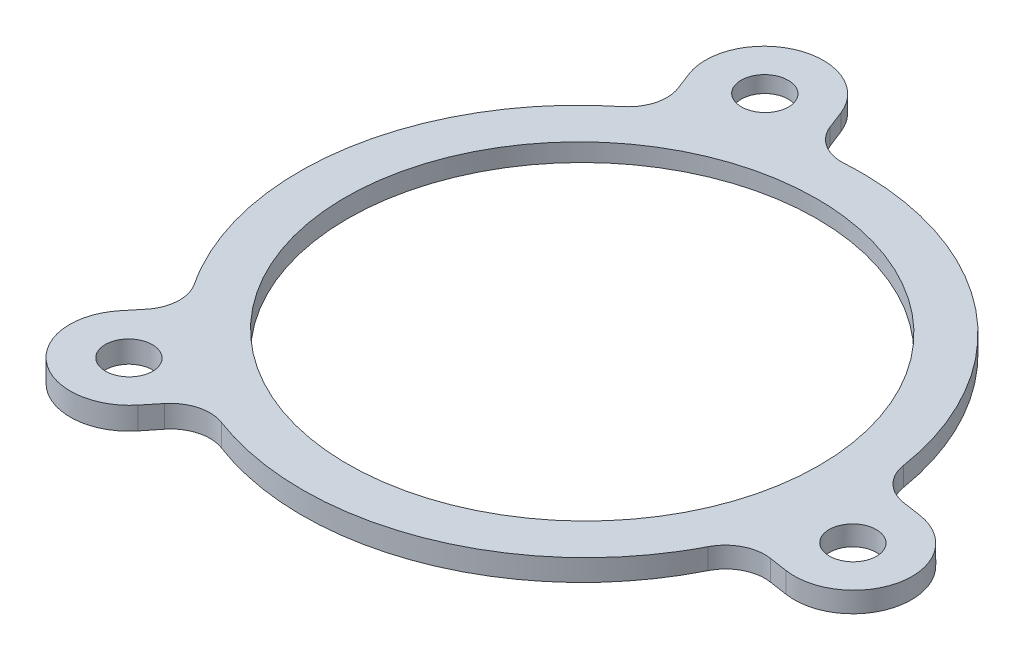
SolidWorks part; units mm, degrees
material "5454-O"
ref_plane "Front Plane" through (0, 0, 0) normal (0, 0, 1) x (1, 0, 0)
ref_plane "Top Plane" through (0, 0, 0) normal (0, 1, 0) x (1, 0, 0)
ref_plane "Right Plane" through (0, 0, 0) normal (1, 0, 0) x (0, 0, -1)
sketch "Sketch1" plane through (0, 0, 0) normal (0, 0, 1) x (1, 0, 0)
  line L0 (-3.7459, 1) -> (5.6477, 1) construction
  dimension "D1" = 1
ref_plane "Plane1" through (0, 0.9999, -0.0099) normal (0, 1, -0.0099) x (1, 0, 0)
sketch "Sketch2" plane through (0, 0, 0) normal (0, 1, 0) x (1, 0, 0)
  line L0 (0, 0) -> (-6.0205, 15.3624) construction
  line L1 (0, 0) -> (-10.294, -12.8951) construction
  line L2 (0, 0) -> (16.3145, -2.4673) construction
  line L3 (-6.0205, 15.3624) -> (-3.2273, 16.4571) construction
  line L4 (-6.0205, 15.3624) -> (-8.8136, 14.2678) construction
  line L5 (-3.2273, 16.4571) -> (-2.3151, 14.1294) construction
  line L6 (-8.8136, 14.2678) -> (-7.9014, 11.9402) construction
  line L7 (16.3145, -2.4673) -> (16.7631, 0.4989) construction
  line L8 (16.3145, -2.4673) -> (15.8659, -5.4336) construction
  line L9 (16.7631, 0.4989) -> (14.2912, 0.8728) construction
  line L10 (15.8659, -5.4336) -> (13.394, -5.0598) construction
  line L11 (-10.294, -12.8951) -> (-7.9495, -14.7667) construction
  line L12 (-10.294, -12.8951) -> (-12.6386, -11.0234) construction
  line L13 (-12.6386, -11.0234) -> (-11.0789, -9.0696) construction
  line L14 (-7.9495, -14.7667) -> (-6.3898, -12.8129) construction
  line L15 (-8.8136, 14.2678) -> (-8.4608, 13.3674)
  line L16 (-3.2273, 16.4571) -> (-2.8744, 15.5566)
  line L17 (16.7631, 0.4989) -> (15.8069, 0.6436)
  line L18 (15.8659, -5.4336) -> (14.9097, -5.289)
  line L19 (-7.9495, -14.7667) -> (-7.3461, -14.0109)
  line L20 (-12.6386, -11.0234) -> (-12.0352, -10.2676)
  arc A0 (-8.8136, 14.2678) -> (-3.2273, 16.4571) centre (-6.0205, 15.3624) cw
  arc A1 (16.7631, 0.4989) -> (15.8659, -5.4336) centre (16.3145, -2.4673) cw
  arc A2 (-7.9495, -14.7667) -> (-12.6386, -11.0234) centre (-10.294, -12.8951) cw
  arc A3 (-0.8882, 14.2902) -> (14.1319, 2.2998) centre (0, 0) cw
  arc A4 (12.8198, -6.3759) -> (-5.0743, -13.3885) centre (0, 0) cw
  arc A5 (-11.9316, -7.9144) -> (-9.0576, 11.0887) centre (0, 0) cw
  arc A6 (-11.9316, -7.9144) -> (-12.0352, -10.2676) centre (-13.5983, -9.0199) cw
  arc A7 (12.8198, -6.3759) -> (14.9097, -5.289) centre (14.6106, -7.2665) cw
  arc A8 (-0.8882, 14.2902) -> (-2.8744, 15.5566) centre (-1.0123, 16.2864) cw
  arc A9 (-7.3461, -14.0109) -> (-5.0743, -13.3885) centre (-5.7831, -15.2587) cw
  arc A10 (15.8069, 0.6436) -> (14.1319, 2.2998) centre (16.1059, 2.6211) cw
  arc A11 (-9.0576, 11.0887) -> (-8.4608, 13.3674) centre (-10.3229, 12.6376) ccw
  circle A12 centre (0, 0) radius 12
  circle A13 centre (-6.0205, 15.3624) radius 1.2
  circle A14 centre (16.3145, -2.4673) radius 1.2
  circle A15 centre (-10.294, -12.8951) radius 1.2
  dimension "D1" = 2
  dimension "D2" = 2
extrude "Boss-Extrude1" add sketch "Sketch2" along normal up to surface (0.8581 mm away) up to plane "Plane1"
sketch3d "3DSketch1"
  point P0 (-15.3178, 1.4981, -19.3624)
